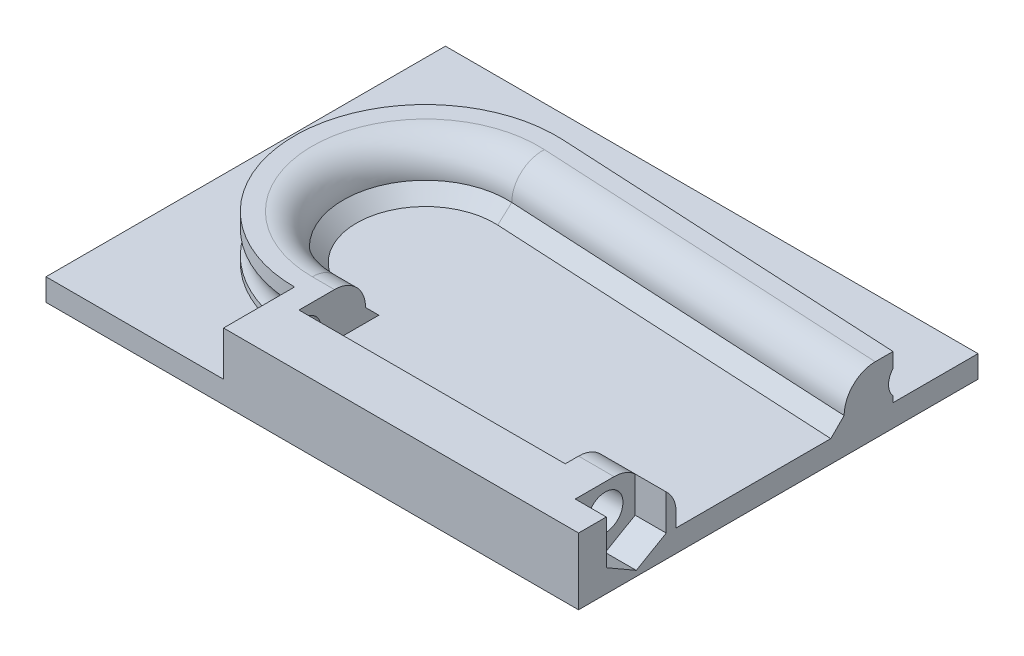
SolidWorks part; units mm, degrees
other "Camera1"
ref_plane "Front Plane" through (0, 0, 0) normal (0, 0, 1) x (1, 0, 0)
ref_plane "Top Plane" through (0, 0, 0) normal (0, 1, 0) x (1, 0, 0)
ref_plane "Right Plane" through (0, 0, 0) normal (1, 0, 0) x (0, 0, -1)
sketch "Sketch1" plane through (0, 0, 0) normal (0, 1, 0) x (1, 0, 0)
  line L1 (-60, 45) -> (60, 45)
  line L2 (-60, 45) -> (-60, -45)
  line L3 (-60, -45) -> (60, -45)
  line L4 (60, 45) -> (60, -45)
  line L5 (-60, 45) -> (60, -45) construction
  line L6 (-60, -45) -> (60, 45) construction
  point P0 (0, 0)
  dimension "D1" = 120
  dimension "D2" = 90
extrude "Boss-Extrude1" add sketch "Sketch1" along normal blind 5
sketch "Sketch2" plane through (0, 5, 0) normal (0, 1, 0) x (1, 0, 0)
  line L0 (-20, -29) -> (-73.0657, -29) construction
  line L1 (60, -45) -> (-20, -45)
  line L2 (60, -45) -> (60, -29)
  line L4 (-20, -45) -> (-20, -29)
  line L5 (-20, -24) -> (-20, 30) construction
  line L6 (60, 25.8479) -> (-18.4561, 29.9596)
  line L7 (60, -45) -> (60, 45) construction
  line L8 (60, 25.8479) -> (60, -29)
  arc A0 (-18.4561, 29.9596) -> (-20, -29) centre (-20, 0.5) ccw
  dimension "D2" = 59
  dimension "D3" = 87
  dimension "D4" = 80
  dimension "D1" = 16
  dimension "D5" = 16
extrude "Boss-Extrude2" add sketch "Sketch2" along normal blind 10
sketch "Sketch3" plane through (60, 0, 0) normal (1, 0, 0) x (0, 0, -1)
  line L0 (25.8479, 5) -> (-48.4082, 5) construction
  line L1 (-45, 15) -> (-45, 0) construction
  circle A0 centre (-32, 9) radius 4
  dimension "D1" = 8
  dimension "D2" = 4
  dimension "D3" = 13
ref_plane "Plane1" through (0, 9, 0) normal (0, 1, 0) x (1, 0, 0)
sketch "Sketch4" plane through (0, 9, 0) normal (0, 1, 0) x (1, 0, 0)
  line L0 (60, -32) -> (-20, -32)
  line L1 (60, -36) -> (60, -28) construction
  line L2 (60, 28.852) -> (-18.2991, 32.9555)
  line L3 (60, 25.8479) -> (-18.4561, 29.9596) construction
  line L4 (60, 25.8479) -> (60, 45) construction
  line L8 (60, 28.852) -> (81.6855, 27.7155)
  arc A0 (-20, -32) -> (-18.2991, 32.9555) centre (-20, 0.5) cw
  dimension "D1" = 32.5
  dimension "D2" = 3
  dimension "D3" = 3
  dimension "D4" = 21.7153
sweep "Cut-Sweep1" cut profiles "Sketch3" path "Sketch4"
sketch "Sketch5" plane through (0, 15, 0) normal (0, 1, 0) x (1, 0, 0)
  line L0 (-15, -18) -> (-15, -33)
  line L1 (-15, -33) -> (45, -33)
  line L2 (60, -23) -> (60, 14.8328)
  line L3 (60, 25.8479) -> (-18.4561, 29.9596) construction
  line L4 (-20, -29) -> (-20, -45) construction
  line L5 (60, -45) -> (60, 25.8479) construction
  line L6 (45, -33) -> (45, -23)
  line L7 (45, -23) -> (60, -23)
  line L8 (-20, -18) -> (-15, -18)
  line L10 (-19.0318, 18.9746) -> (60, 14.8328)
  line L12 (49, -34) -> (49, 15.4093)
  line L13 (49, 15.4093) -> (-19.0318, 18.9746)
  line L14 (-9, -14.3745) -> (-9, -34)
  line L15 (-9, -34) -> (49, -34)
  arc A3 (-19.0318, 18.9746) -> (-9, -14.3745) centre (-20, 0.5) ccw
  arc A4 (-19.0318, 18.9746) -> (-20, -18) centre (-20, 0.5) ccw
  point P0 (-15, -18)
  dimension "D4" = 15
  dimension "D2" = 5
  dimension "D3" = 15
  dimension "D5" = 10
  dimension "D1" = 11
extrude "Cut-Extrude1" cut sketch "Sketch5" against normal blind 10
chamfer "Chamfer2" distance 3 angle 45 3 edges at (-17.5, 5, 18) (20.4841, 5, -16.9037) (-38.4937, 5, -0.9843)
fillet "Fillet1" radius 7 4 edges at (-17.5, 15, 18) (-38.4937, 15, -0.9843) (20.4841, 15, -16.9037) (52.5, 15, 23)
sketch "Sketch6" plane through (60, 0, 0) normal (1, 0, 0) x (0, 0, -1)
  line L1 (-32, 1.2058) -> (-25.25, 5.1029)
  line L6 (-38.75, 5.1029) -> (-32, 1.2058)
  line L7 (-45, 15) -> (-45, 0) construction
  line L11 (-35.1077, 15) -> (-35.375, 14.8457) [skipped]
  line L12 (-28.625, 14.8457) -> (-28.8923, 15) [skipped]
  line L13 (-38.75, 12.8971) -> (-38.75, 5.1029) [skipped]
  line L14 (-25.25, 5.1029) -> (-25.25, 12.8971) [skipped]
  line L15 (-38.75, 5.1029) -> (-38.75, 15)
  line L16 (-45, 15) -> (-30, 15) construction
  line L17 (-38.75, 15) -> (-25.25, 15)
  line L18 (-25, 15) -> (-33, 15) construction
  line L19 (-25.25, 15) -> (-25.25, 5.1029)
  dimension "D1" = 13.5
  dimension "D2" = 9.8971
  dimension "D3" = 9.8971
  dimension "D4" = 7.7942
  dimension "D5" = 6.25
extrude "Cut-Extrude2" cut sketch "Sketch6" against normal blind 7
